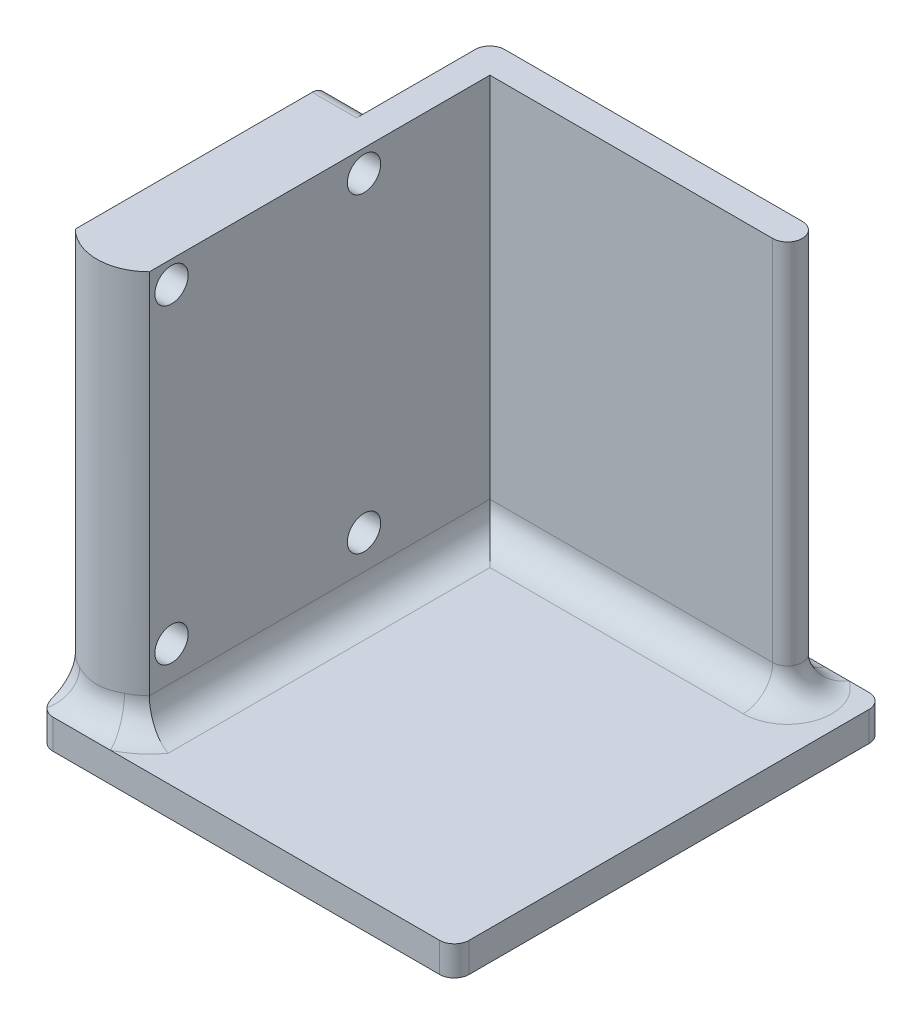
SolidWorks part; units mm, degrees
ref_plane "Front Plane" through (0, 0, 0) normal (0, 0, 1) x (1, 0, 0)
ref_plane "Top Plane" through (0, 0, 0) normal (0, 1, 0) x (1, 0, 0)
ref_plane "Right Plane" through (0, 0, 0) normal (1, 0, 0) x (0, 0, -1)
sketch "Sketch5" plane through (0, 0, 0) normal (0, 1, 0) x (1, 0, 0)
  line L0 (-1000, 0) -> (49000, 0) construction
sketch "Sketch1" plane through (0, 0, 0) normal (0, 1, 0) x (1, 0, 0)
  line L0 (-201000, 0) -> (249000, 0) construction
  line L1 (-28.1, 34) -> (0, 34)
  line L2 (-28.1, 34) -> (-28.1, 5)
  line L3 (-28.1, 5) -> (0, 5)
  line L4 (0, 34) -> (0, 5)
  line L5 (-28.1, 34) -> (0, 5) construction
  line L6 (-28.1, 5) -> (0, 34) construction
  point P0 (-14.05, 19.5)
  dimension "D1" = 29
  dimension "D2" = 28.1
  dimension "D3" = 5
  dimension "D4" = 0
extrude "Boss-Extrude1" add sketch "Sketch1" along normal blind 2
sketch "Sketch2" plane through (0, 2, 0) normal (0, 1, 0) x (1, 0, 0)
  line L0 (-28.1, 19.5) -> (0, 19.5) construction
  line L1 (-24.1, 31.5) -> (-24.1, 7.5) construction
  line L2 (-23.1, 31.5) -> (-23.1, 7.5)
  line L3 (-25.1, 31.5) -> (-25.1, 7.5)
  line L4 (0, 5) -> (0, 34)
  line L5 (0, 34) -> (-28.1, 34)
  line L6 (-28.1, 34) -> (-28.1, 5)
  line L7 (-28.1, 5) -> (0, 5)
  line L8 (0, 5) -> (0, 34)
  line L9 (0, 34) -> (-28.1, 34)
  line L10 (-28.1, 34) -> (-28.1, 5)
  line L11 (-28.1, 5) -> (0, 5)
  line L12 (-25.1, 7.5) -> (-23.1, 7.5) construction
  line L13 (-1000, 0) -> (49000, 0) construction
  line L16 (-24.1, 31.5) -> (-4, 31.5) construction
  line L17 (-24.1, 32.5) -> (-4, 32.5)
  line L18 (-24.1, 30.5) -> (-4, 30.5)
  line L23 (-25.1, 7.5) -> (-28.1, 7.5)
  arc A0 (-23.1, 31.5) -> (-25.1, 31.5) centre (-24.1, 31.5) ccw
  arc A4 (-24.1, 32.5) -> (-24.1, 30.5) centre (-24.1, 31.5) ccw
  arc A5 (-4, 30.5) -> (-4, 32.5) centre (-4, 31.5) ccw
  arc A8 (-23.1, 7.5) -> (-28.1, 7.5) centre (-25.6, 10) cw
  point P8 (-24.15, 19.5)
  point P16 (-24.1, 7.5)
  point P24 (-14.05, 31.5)
  dimension "D9" = 3.5355
  dimension "D2" = 24
  dimension "D3" = 2
  dimension "D4" = 3
  dimension "D5" = 2
  dimension "D6" = 4
  dimension "D10" = 2.5
  dimension "D1" = 0
extrude "Boss-Extrude2" add sketch "Sketch2" along normal blind 26.8 contours L3 L23 A8 L2 A0 | L18 A5 L17 A4
sketch "Sketch3" plane through (-25.1, 0, 0) normal (-1, 0, 0) x (0, 0, 1)
  line L0 (-24.5, 27.8) -> (-24.5, 2)
  line L1 (-16, -972.3653) -> (-16, 49027.6347) construction
  line L4 (-31.5, 2) -> (-7.5, 2)
  line L5 (-7.5, 2) -> (-7.5, 28.8)
  line L6 (-7.5, 28.8) -> (-31.5, 28.8)
  line L7 (-31.5, 28.8) -> (-31.5, 2)
  line L10 (-7.5, 28.8) -> (-31.5, 28.8)
  line L11 (-31.5, 28.8) -> (-31.5, 2)
  line L19 (-7.5, 2) -> (-7.5, 28.8)
  line L24 (-31.5, 2) -> (-7.5, 2)
  arc A0 (-24.5, 27.8) -> (-23.5, 28.8) centre (-23.5, 27.8) cw
  dimension "D4" = 1
  dimension "D2" = 17
  dimension "D3" = 8.5
  dimension "D1" = 0
extrude "Boss-Extrude3" add sketch "Sketch3" along normal blind 3
fillet "Fillet1" radius 2 6 edges at (-25.1, 2, -28) (-24.8071, 2, -32.2071) (-23.1, 2, -19) (-3, 2, -31.5) (-13.55, 2, -30.5) (-25.6, 2, -6.4645)
sketch "Sketch4" plane through (-28.1, 0, 0) normal (-1, 0, 0) x (0, 0, 1)
  line L0 (-15.5, -981.5649) -> (-15.5, 49018.4351) construction
  line L1 (-1018.5962, 16.8) -> (48981.4038, 16.8) construction
  line L3 (0, -15.455) -> (0, 15.455) construction
  line L8 (-34, 0) -> (-5, 0)
  line L9 (-5, 0) -> (-5, 2)
  line L10 (-5, 2) -> (-5.0612, 2)
  line L11 (-7.5, 4) -> (-7.5, 28.8)
  line L12 (-7.5, 28.8) -> (-23.5, 28.8)
  line L13 (-24.5, 27.8) -> (-24.5, 2)
  line L14 (-24.5, 2) -> (-34, 2)
  line L15 (-34, 2) -> (-34, 0)
  line L16 (-34, 0) -> (-5, 0)
  line L17 (-5, 0) -> (-5, 2)
  line L18 (-5, 2) -> (-5.0612, 2)
  line L20 (-7.5, 28.8) -> (-23.5, 28.8)
  line L21 (-24.5, 27.8) -> (-24.5, 2)
  line L22 (-24.5, 2) -> (-34, 2)
  line L23 (-34, 2) -> (-34, 0)
  line L27 (-7.5, 4) -> (-7.5, 28.8)
  circle A0 centre (-9, 27.3) radius 1.125
  circle A1 centre (-22, 27.3) radius 1.125
  arc A3 (-23.5, 28.8) -> (-24.5, 27.8) centre (-23.5, 27.8) ccw
  arc A5 (-23.5, 28.8) -> (-24.5, 27.8) centre (-23.5, 27.8) ccw
  circle A6 centre (-9, 6.3) radius 1.125
  circle A7 centre (-22, 6.3) radius 1.125
  circle A8 centre (22, 6.3) radius 1.125
  circle A9 centre (9, 6.3) radius 1.125
  circle A10 centre (9, 27.3) radius 1.125
  circle A11 centre (22, 27.3) radius 1.125
  spline S1 degree 3 poles (642.708, 2930.8179) (82.7236, 229.498) (14.3819, -4.746) (-6.0432, 2.1879) (-6.1776, 2.2458) (-6.4321, 2.38) (-6.5535, 2.4567) (-6.7838, 2.63) (-6.8933, 2.7275) (-7.0901, 2.938) (-7.1785, 3.0517) (-7.3303, 3.2999) (-7.3917, 3.4316) (-10.4756, 13.4587) (84.8646, 61.9514) (1771.1282, -2409.4703) knots -18.341117 -18.341117 -18.341117 -18.341117 0.25 0.25 0.375 0.375 0.5 0.5 0.625 0.625 0.75 0.75 0.875 0.875 9.81921 9.81921 9.81921 9.81921 only from (-5.0612, 2) to (-7.5, 4)
  spline S2 degree 3 poles (-5.0612, 2) (-5.3524, 2) (-5.634, 2.049) (-6.0432, 2.1879) (-6.1776, 2.2458) (-6.4321, 2.38) (-6.5535, 2.4567) (-6.7838, 2.63) (-6.8933, 2.7275) (-7.0901, 2.938) (-7.1785, 3.0517) (-7.3303, 3.2999) (-7.3917, 3.4316) (-7.4767, 3.708) (-7.5, 3.8537) (-7.5, 4) knots 0 0 0 0 0.25 0.25 0.375 0.375 0.5 0.5 0.625 0.625 0.75 0.75 0.875 0.875 1 1 1 1
  dimension "D3" = 2.25
  dimension "D2" = 1.5
  dimension "D4" = 8
  dimension "D5" = 1.5
  dimension "D6" = 4.3
  dimension "D1" = 0
extrude "Cut-Extrude1" cut sketch "Sketch4" against normal through all contours A0 | A7 | A6 | A1 | A10 | A11 | A8 | A9
fillet "Fillet2" radius 1 4 edges at (-28.1, 1, -34) (0, 1, -34) (-28.1, 1, -5) (0, 1, -5)
